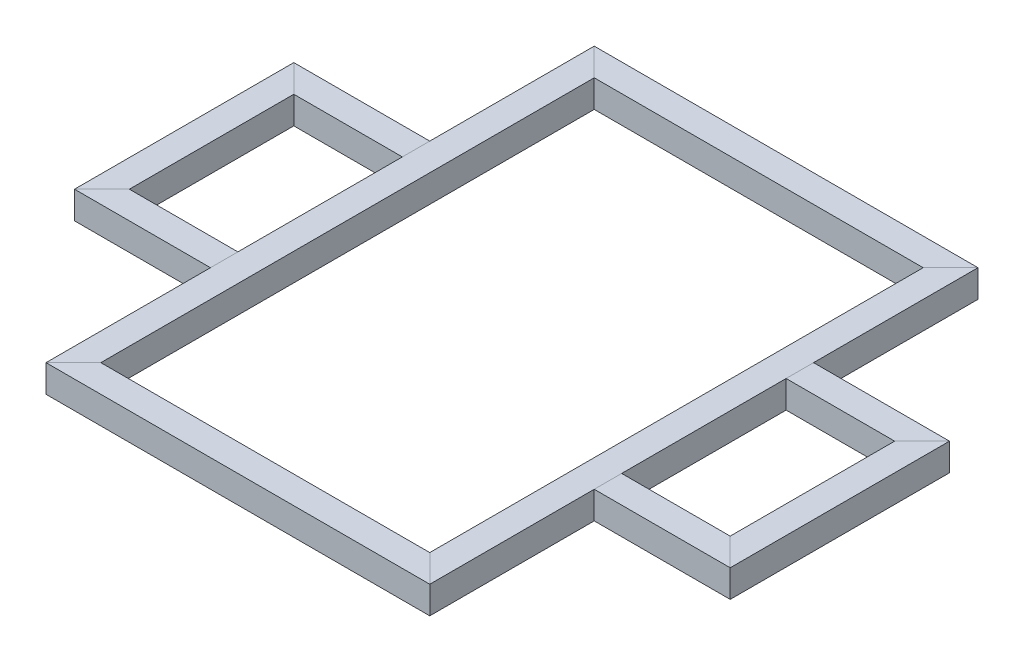
SolidWorks part; units mm, degrees
ref_plane "Front Plane" through (0, 0, 0) normal (0, 0, 1) x (1, 0, 0)
ref_plane "Top Plane" through (0, 0, 0) normal (0, 1, 0) x (1, 0, 0)
ref_plane "Right Plane" through (0, 0, 0) normal (1, 0, 0) x (0, 0, -1)
sketch "Sketch1" plane through (0, 0, 0) normal (0, 0, 1) x (1, 0, 0)
  line L1 (-175, -12.5) -> (-150, -12.5)
  line L2 (-175, -12.5) -> (-175, 12.5)
  line L3 (-175, 12.5) -> (-150, 12.5)
  line L4 (-150, -12.5) -> (-150, 12.5)
  line L5 (-175, -12.5) -> (-150, 12.5) construction
  line L6 (-175, 12.5) -> (-150, -12.5) construction
  line L10 (-173, 10.5) -> (-152, 10.5)
  line L11 (-152, -10.5) -> (-152, 10.5)
  line L12 (-173, -10.5) -> (-152, -10.5)
  line L13 (-173, -10.5) -> (-173, 10.5)
  line L14 (0, 12.5) -> (0, 0) construction
  line L15 (173, 10.5) -> (152, 10.5)
  line L16 (152, -10.5) -> (152, 10.5)
  line L17 (150, -12.5) -> (150, 12.5)
  line L18 (175, -12.5) -> (150, -12.5)
  line L19 (173, -10.5) -> (152, -10.5)
  line L20 (173, -10.5) -> (173, 10.5)
  line L21 (175, -12.5) -> (175, 12.5)
  line L22 (175, 12.5) -> (150, 12.5)
  point P0 (0, 0)
  point P12 (-162.5, 0)
  dimension "D1" = 25
  dimension "D2" = 2
  dimension "D3" = 150
extrude "Boss-Extrude1" add sketch "Sketch1" along normal mid plane 500
sketch "Sketch2" plane through (0, 12.5, 0) normal (0, 1, 0) x (1, 0, 0)
  line L0 (-175, 250) -> (-150, 225)
  line L1 (-150, -250) -> (-150, 250) construction
  line L2 (-150, 225) -> (-150, 250)
  line L3 (-150, 250) -> (-175, 250)
  line L4 (175, 250) -> (150, 225)
  line L5 (150, -250) -> (150, 250) construction
  line L6 (150, 225) -> (150, 250)
  line L8 (150, 250) -> (175, 250)
  line L9 (-175, -250) -> (-150, -225)
  line L10 (-150, -225) -> (-150, -250)
  line L11 (-150, -250) -> (-175, -250)
  line L12 (175, -250) -> (150, -225)
  line L13 (150, -225) -> (150, -250)
  line L14 (150, -250) -> (175, -250)
extrude "Cut-Extrude1" cut sketch "Sketch2" against normal through all
sketch "Sketch3" plane through (0, 0, 0) normal (1, 0, 0) x (0, 0, -1)
  line L0 (-250, -12.5) -> (250, -12.5) construction
  line L1 (-250, 12.5) -> (-225, 12.5)
  line L2 (-250, 12.5) -> (-250, -12.5)
  line L3 (-250, -12.5) -> (-225, -12.5)
  line L4 (-225, 12.5) -> (-225, -12.5)
  line L5 (-248, 10.5) -> (-227, 10.5)
  line L6 (-227, 10.5) -> (-227, -10.5)
  line L7 (-248, -10.5) -> (-227, -10.5)
  line L8 (-248, 10.5) -> (-248, -10.5)
  line L9 (0, 0) -> (0, 12.5) construction
  line L10 (-250, 12.5) -> (250, 12.5) construction
  line L11 (248, 10.5) -> (248, -10.5)
  line L12 (248, -10.5) -> (227, -10.5)
  line L13 (227, 10.5) -> (227, -10.5)
  line L14 (248, 10.5) -> (227, 10.5)
  line L15 (225, 12.5) -> (225, -12.5)
  line L16 (250, -12.5) -> (225, -12.5)
  line L17 (250, 12.5) -> (250, -12.5)
  line L18 (250, 12.5) -> (225, 12.5)
  dimension "D1" = 2
extrude "Boss-Extrude2" add sketch "Sketch3" along normal mid plane 350 separate body
sketch "Sketch4" plane through (0, 12.5, 0) normal (0, 1, 0) x (1, 0, 0)
  line L0 (-175, 250) -> (-175, 225)
  line L1 (-175, 225) -> (-150, 225)
  line L2 (175, 225) -> (-175, 225) construction
  line L3 (-150, 225) -> (-175, 250)
  line L4 (175, 250) -> (150, 225)
  line L5 (150, 225) -> (175, 225)
  line L6 (175, 225) -> (175, 250)
  line L7 (0, 0) -> (175, 0) construction
  line L8 (175, -225) -> (175, -250)
  line L9 (150, -225) -> (175, -225)
  line L10 (175, -250) -> (150, -225)
  line L11 (-150, -225) -> (-175, -250)
  line L12 (-175, -225) -> (-150, -225)
  line L13 (-175, -250) -> (-175, -225)
extrude "Cut-Extrude2" cut sketch "Sketch4" against normal through all
sketch "Sketch5" plane through (-175, 0, 0) normal (-1, 0, 0) x (0, 0, 1)
  line L0 (250, 12.5) -> (-250, 12.5) construction
  line L1 (-100, 12.5) -> (-75, 12.5)
  line L2 (-100, 12.5) -> (-100, -12.5)
  line L3 (-100, -12.5) -> (-75, -12.5)
  line L4 (-75, 12.5) -> (-75, -12.5)
  line L5 (250, -12.5) -> (-250, -12.5) construction
  line L6 (-75, 0) -> (0, 0) construction
  line L7 (75, 12.5) -> (100, 12.5)
  line L8 (75, 12.5) -> (75, -12.5)
  line L9 (75, -12.5) -> (100, -12.5)
  line L10 (100, 12.5) -> (100, -12.5)
  line L11 (0, 0) -> (75, 0) construction
  line L12 (-98, 10.5) -> (-77, 10.5)
  line L13 (-77, 10.5) -> (-77, -10.5)
  line L14 (-98, -10.5) -> (-77, -10.5)
  line L15 (-98, 10.5) -> (-98, -10.5)
  line L16 (77, 10.5) -> (98, 10.5)
  line L17 (98, 10.5) -> (98, -10.5)
  line L18 (77, -10.5) -> (98, -10.5)
  line L19 (77, 10.5) -> (77, -10.5)
  dimension "D1" = 150
  dimension "D2" = 2
extrude "Boss-Extrude3" add sketch "Sketch5" along normal blind 124 separate body
sketch "Sketch6" plane through (0, 12.5, 0) normal (0, 1, 0) x (1, 0, 0)
  line L0 (-299, 100) -> (-299, 75)
  line L1 (-299, 75) -> (-274, 75)
  line L2 (-299, 75) -> (-175, 75) construction
  line L3 (-274, 75) -> (-299, 100)
  line L4 (-299, -100) -> (-299, -75)
  line L5 (-299, -100) -> (-299, -75) construction
  line L6 (-299, -75) -> (-274, -75)
  line L7 (-299, -75) -> (-175, -75) construction
  line L8 (-274, -75) -> (-299, -100)
  line L9 (-299, -100) -> (-175, -100) construction
extrude "Cut-Extrude3" cut sketch "Sketch6" against normal through all
sketch "Sketch7" plane through (0, 0, 0) normal (0, 0, 1) x (1, 0, 0)
  line L0 (-297, 10.5) -> (-276, 10.5)
  line L1 (-299, 12.5) -> (-274, 12.5)
  line L2 (-299, 12.5) -> (-299, -12.5)
  line L3 (-299, -12.5) -> (-274, -12.5)
  line L4 (-274, 12.5) -> (-274, -12.5)
  line L5 (-276, 10.5) -> (-276, -10.5)
  line L6 (-297, -10.5) -> (-276, -10.5)
  line L7 (-297, 10.5) -> (-297, -10.5)
  dimension "D1" = 2
extrude "Boss-Extrude4" add sketch "Sketch7" along normal mid plane 200 separate body
sketch "Sketch8" plane through (0, 12.5, 0) normal (0, 1, 0) x (1, 0, 0)
  line L0 (-299, 100) -> (-274, 75)
  line L1 (-274, 75) -> (-274, 100)
  line L3 (-274, 100) -> (-299, 100)
  line L4 (-299, 100) -> (-175, 100) construction
  line L5 (-274, -75) -> (-274, -100)
  line L6 (-299, -100) -> (-175, -100) construction
  line L7 (-274, -100) -> (-299, -100)
  line L8 (-299, -100) -> (-274, -75)
extrude "Cut-Extrude4" cut sketch "Sketch8" against normal through all
mirror "Mirror1" about plane through (0, 0, 0) normal (1, 0, 0) of bodies 111 114 112
sketch "Sketch9" plane through (0, 0, 0) normal (0, 1, 0) x (1, 0, 0)
  line L0 (-300, 250) -> (-300, -250)
  line L1 (-300, -250) -> (300, -250)
  line L2 (300, -250) -> (300, 250)
  line L3 (300, 250) -> (200, 350)
  line L4 (200, 350) -> (-200, 350)
  line L5 (-200, 350) -> (-300, 250)
  line L6 (0, 350) -> (0, 0) construction
  dimension "D1" = 600
  dimension "D2" = 250
  dimension "D3" = 600
  dimension "D4" = 250
  dimension "D5" = 45
